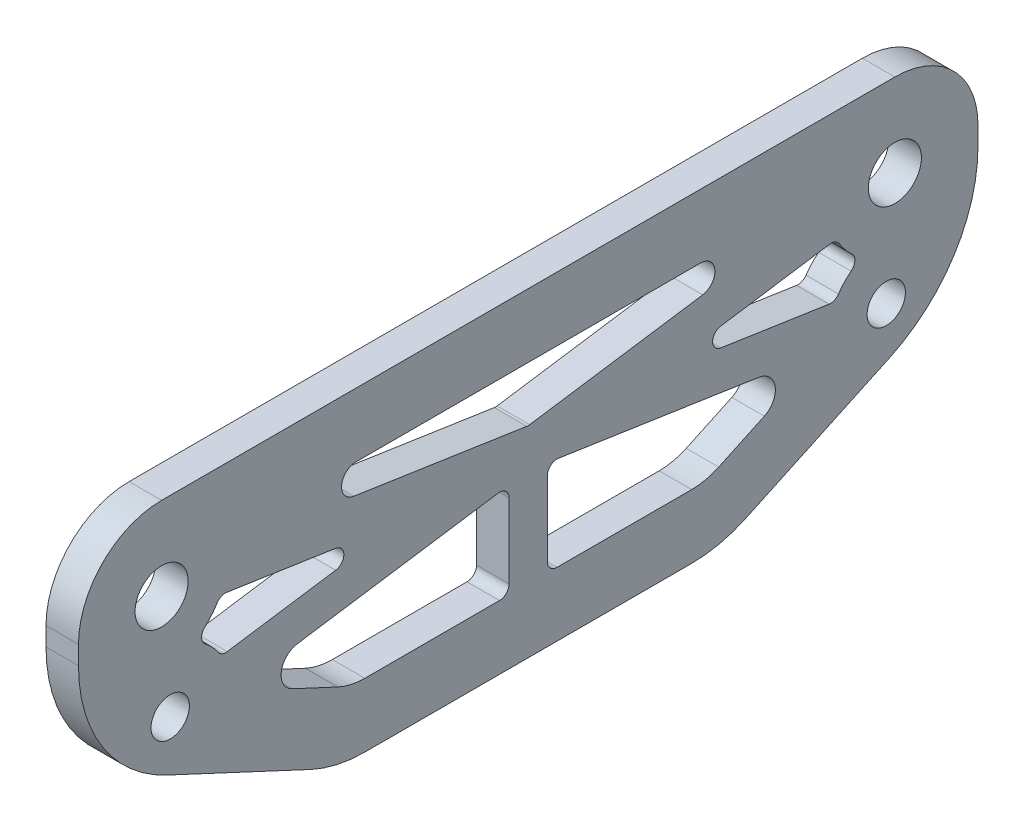
SolidWorks part; units mm, degrees
ref_plane "Front Plane" through (0, 0, 0) normal (0, 0, 1) x (1, 0, 0)
ref_plane "Top Plane" through (0, 0, 0) normal (0, 1, 0) x (1, 0, 0)
ref_plane "Right Plane" through (0, 0, 0) normal (1, 0, 0) x (0, 0, -1)
sketch "Sketch1" plane through (0, 0, 0) normal (1, 0, 0) x (0, 0, -1)
  line L0 (15, 12.5) -> (28.675, 12.5)
  line L1 (-15, -12.5) -> (15, -12.5)
  line L3 (-15, 12.5) -> (15, 12.5)
  line L5 (-15, -12.5) -> (15, 12.5) construction
  line L6 (-15, 12.5) -> (15, -12.5) construction
  line L8 (0, 12.5) -> (0, -12.5) construction
  line L10 (-15, 12.5) -> (-28.675, 12.5)
  line L11 (23.175, 193.3555) -> (23.175, -34.0445) construction
  line L13 (35.175, 6) -> (35.175, 4.5526)
  line L14 (28.2464, -6.3231) -> (15, -12.5)
  line L16 (-35.175, 6) -> (-35.175, 4.5526)
  line L17 (-28.2464, -6.3231) -> (-15, -12.5)
  arc A0 (28.675, 12.5) -> (35.175, 6) centre (28.675, 6) cw
  circle A1 centre (28.675, 6) radius 5.5 construction
  circle A2 centre (-28.675, 6) radius 5.5 construction
  arc A3 (-28.675, 12.5) -> (-35.175, 6) centre (-28.675, 6) ccw
  arc A4 (35.175, 4.5526) -> (28.2464, -6.3231) centre (23.175, 4.5526) cw
  circle A5 centre (28.675, 6) radius 2.075
  arc A6 (-35.175, 4.5526) -> (-28.2464, -6.3231) centre (-23.175, 4.5526) ccw
  circle A9 centre (-28.675, 6) radius 2.075
  circle A11 centre (28, -2.5) radius 1.5
  circle A12 centre (-28, -2.5) radius 1.5
  point P0 (0, 0)
  point P28 (0, 0)
  dimension "D1" = 11
  dimension "D2" = 1
  dimension "D3" = 4.15
  dimension "D4" = 3
  dimension "D6" = 25
  dimension "D8" = 12
  dimension "D5" = 25
  dimension "D7" = 30
  dimension "D9" = 28
  dimension "D10" = 2.5
extrude "Boss-Extrude1" add sketch "Sketch1" along normal blind 2.54
fillet "Fillet1" radius 10 2 edges at (1.27, -12.5, -15) (1.27, -12.5, 15)
sketch "Sketch2" plane through (0, 0, 0) normal (1, 0, 0) x (0, 0, -1)
  line L0 (-28.675, 6) -> (28, -2.5) construction
  line L10 (-28.675, -2.6012) -> (28.675, 6)
  line L11 (-28.675, 6) -> (28, -2.5)
  line L12 (-28.8975, 4.5166) -> (27.7775, -3.9834)
  line L13 (-28.4525, 7.4834) -> (28.2225, -1.0166)
  line L14 (-28.8975, 4.5166) -> (-28.4525, 7.4834)
  line L15 (27.7775, -3.9834) -> (28.2225, -1.0166)
  line L16 (-12.7831, -7.5) -> (12.7831, -7.5)
  line L17 (14.8961, -7.0315) -> (26.1333, -1.7916)
  line L18 (30.175, 4.5526) -> (30.175, 6)
  line L19 (28.675, 7.5) -> (-28.675, 7.5)
  line L20 (-30.175, 6) -> (-30.175, 4.5526)
  line L21 (-26.1333, -1.7916) -> (-14.8961, -7.0315)
  line L22 (-12.7831, -7.5) -> (12.7831, -7.5)
  line L23 (14.8961, -7.0315) -> (26.1333, -1.7916)
  line L24 (30.175, 4.5526) -> (30.175, 6)
  line L25 (28.675, 7.5) -> (-28.675, 7.5)
  line L26 (-30.175, 6) -> (-30.175, 4.5526)
  line L27 (-26.1333, -1.7916) -> (-14.8961, -7.0315)
  line L28 (-28.4525, -4.0846) -> (28.8975, 4.5166)
  line L29 (-28.8975, -1.1178) -> (28.4525, 7.4834)
  line L30 (-28.4525, -4.0846) -> (-28.8975, -1.1178)
  line L31 (28.8975, 4.5166) -> (28.4525, 7.4834)
  line L32 (0, -7.5) -> (0, 7.5) construction
  line L33 (0, 1.6994) -> (0, -7.5)
  line L34 (-1.5, 1.6994) -> (-1.5, -7.5)
  line L35 (1.5, 1.6994) -> (1.5, -7.5)
  line L36 (-1.5, 1.6994) -> (1.5, 1.6994)
  line L37 (-1.5, -7.5) -> (1.5, -7.5)
  arc A0 (-18.0527, -2.5249) -> (-18.4641, -5.3678) centre (-17.8302, -4.0083) ccw
  arc A1 (18.0527, -2.5249) -> (18.4641, -5.3678) centre (17.8302, -4.0083) cw
  circle A2 centre (-28, -2.5) radius 4.5
  circle A3 centre (-28, -2.5) radius 4.5
  circle A5 centre (28, -2.5) radius 4.5
  circle A6 centre (28, -2.5) radius 4.5
  circle A11 centre (-28.675, 6) radius 5.075
  arc A12 (12.7831, -7.5) -> (14.8961, -7.0315) centre (12.7831, -2.5) ccw
  arc A13 (26.1333, -1.7916) -> (30.175, 4.5526) centre (23.175, 4.5526) ccw
  arc A14 (30.175, 6) -> (28.675, 7.5) centre (28.675, 6) ccw
  arc A15 (-28.675, 7.5) -> (-30.175, 6) centre (-28.675, 6) ccw
  arc A16 (-30.175, 4.5526) -> (-26.1333, -1.7916) centre (-23.175, 4.5526) ccw
  arc A17 (-14.8961, -7.0315) -> (-12.7831, -7.5) centre (-12.7831, -2.5) ccw
  arc A18 (12.7831, -7.5) -> (14.8961, -7.0315) centre (12.7831, -2.5) ccw
  arc A19 (26.1333, -1.7916) -> (30.175, 4.5526) centre (23.175, 4.5526) ccw
  arc A20 (30.175, 6) -> (28.675, 7.5) centre (28.675, 6) ccw
  arc A21 (-28.675, 7.5) -> (-30.175, 6) centre (-28.675, 6) ccw
  arc A22 (-30.175, 4.5526) -> (-26.1333, -1.7916) centre (-23.175, 4.5526) ccw
  arc A23 (-14.8961, -7.0315) -> (-12.7831, -7.5) centre (-12.7831, -2.5) ccw
  circle A24 centre (-28.675, 6) radius 5.075
  circle A26 centre (28.675, 6) radius 5.075
  circle A27 centre (28.675, 6) radius 5.075
  arc A32 (13.477, 7.5) -> (13.6439, 5.2624) centre (13.477, 6.375) cw
  arc A33 (-13.477, 7.5) -> (-13.6439, 5.2624) centre (-13.477, 6.375) ccw
  dimension "D11" = 3
  dimension "D12" = 1.125
  dimension "D2" = 1.5
  dimension "D1" = 5
  dimension "D3" = 3
  dimension "D4" = 3
  dimension "D6" = 1.5
  dimension "D7" = 1.5
  dimension "D8" = 1.5
  dimension "D9" = 1.5
  dimension "D13" = 1.5
  dimension "D14" = 1.5
  dimension "D15" = 3
extrude "Cut-Extrude2" cut sketch "Sketch2" along normal through all contours A24 A3 L29 L12 | A27 L28 L13 A6 | L25 A33 L13 L29 A32 | A1 L12 L35 L22 | L28 A0 L22 L34 region at (0, 1.7005, 19.9688) region at (0, -4.2389, 9.1911) region at (0, 5.8357, 0) region at (0, -4.2389, -9.1911) region at (0, 1.7005, -19.9688)
fillet "Fillet2" radius 0.75 13 edges at (1.27, -7.5, -1.5) (1.27, 3.7975, -24.1028) (1.27, 1.6994, -10.1133) (1.27, 3.7975, 24.1028) (1.27, 3.2162, 0) (1.27, -0.0424, -1.5) (1.27, -7.5, 1.5) (1.27, -0.0424, 1.5) (1.27, 1.6994, 10.1133) (1.27, -0.3873, -24.0268) (1.27, 1.6002, -26.1457) (1.27, -0.3873, 24.0268) (1.27, 1.6002, 26.1457)
